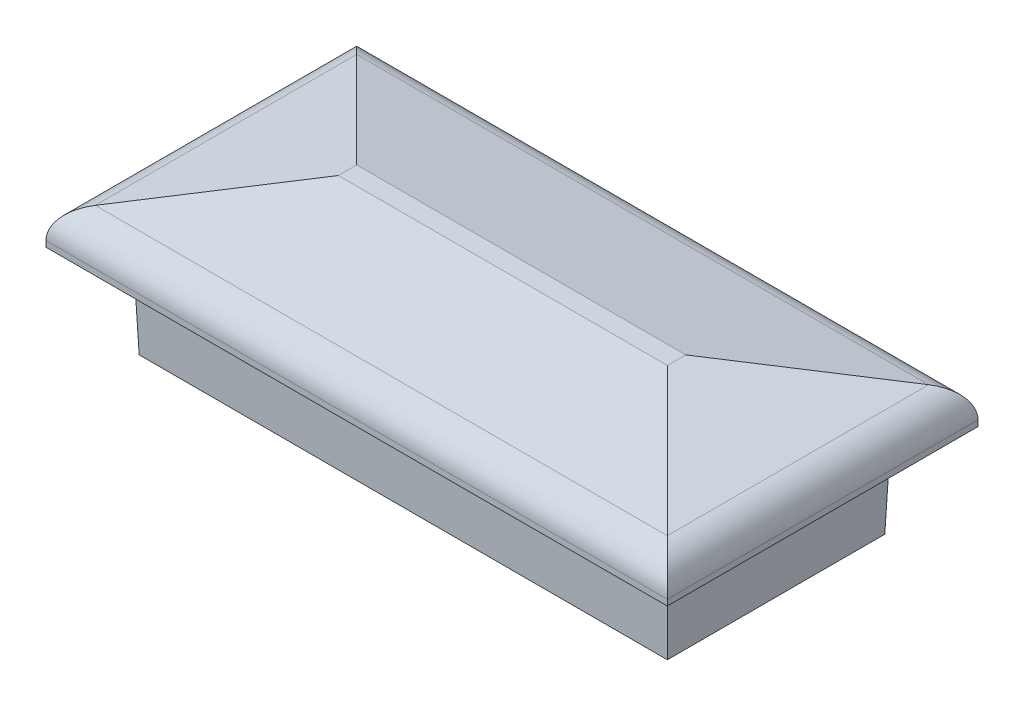
SolidWorks part; units mm, degrees
ref_plane "Front Plane" through (0, 0, 0) normal (0, 0, 1) x (1, 0, 0)
ref_plane "Top Plane" through (0, 0, 0) normal (0, 1, 0) x (1, 0, 0)
ref_plane "Right Plane" through (0, 0, 0) normal (1, 0, 0) x (0, 0, -1)
sketch "Sketch1" plane through (0, 0, 0) normal (0, 1, 0) x (1, 0, 0)
  line L1 (-21.971, 9.271) -> (21.971, 9.271)
  line L2 (-21.971, 9.271) -> (-21.971, -9.271)
  line L3 (-21.971, -9.271) -> (21.971, -9.271)
  line L4 (21.971, 9.271) -> (21.971, -9.271)
  line L5 (-21.971, 9.271) -> (21.971, -9.271) construction
  line L6 (-21.971, -9.271) -> (21.971, 9.271) construction
  point P0 (0, 0)
  dimension "D1" = 43.942
  dimension "D2" = 18.542
extrude "Boss-Extrude1" add sketch "Sketch1" along normal blind 7.62
chamfer "Chamfer1" distance 0.381 angle 88 4 edges at (-21.971, 0, 0) (0, 0, -9.271) (21.971, 0, 0) (0, 0, 9.271) first distance on face at (0, 0, 0)
shell "Shell1" thickness 2.54 removed face at (0, 0, 0)
sketch "Sketch2" plane through (0, 7.62, 0) normal (0, 1, 0) x (1, 0, 0)
  line L1 (25.4, -12.7) -> (-25.4, -12.7)
  line L2 (25.4, -12.7) -> (25.4, 12.7)
  line L3 (25.4, 12.7) -> (-25.4, 12.7)
  line L4 (-25.4, -12.7) -> (-25.4, 12.7)
  line L5 (25.4, -12.7) -> (-25.4, 12.7) construction
  line L6 (25.4, 12.7) -> (-25.4, -12.7) construction
  point P0 (0, 0)
  dimension "D1" = 50.8
  dimension "D2" = 25.4
extrude "Boss-Extrude2" add sketch "Sketch2" along normal blind 5.08
chamfer "Chamfer2" distance 2.54 angle 78 4 edges at (0, 12.7, 12.7) (-25.4, 12.7, 0) (0, 12.7, -12.7) (25.4, 12.7, 0) first distance on face at (0, 10.16, 12.7) first distance on face at (-25.4, 10.16, 0) first distance on face at (0, 10.16, -12.7) first distance on face at (25.4, 10.16, 0)
fillet "Fillet1" radius 2.54 4 edges at (0, 10.16, 12.7) (-25.4, 10.16, 0) (25.4, 10.16, 0) (0, 10.16, -12.7)
